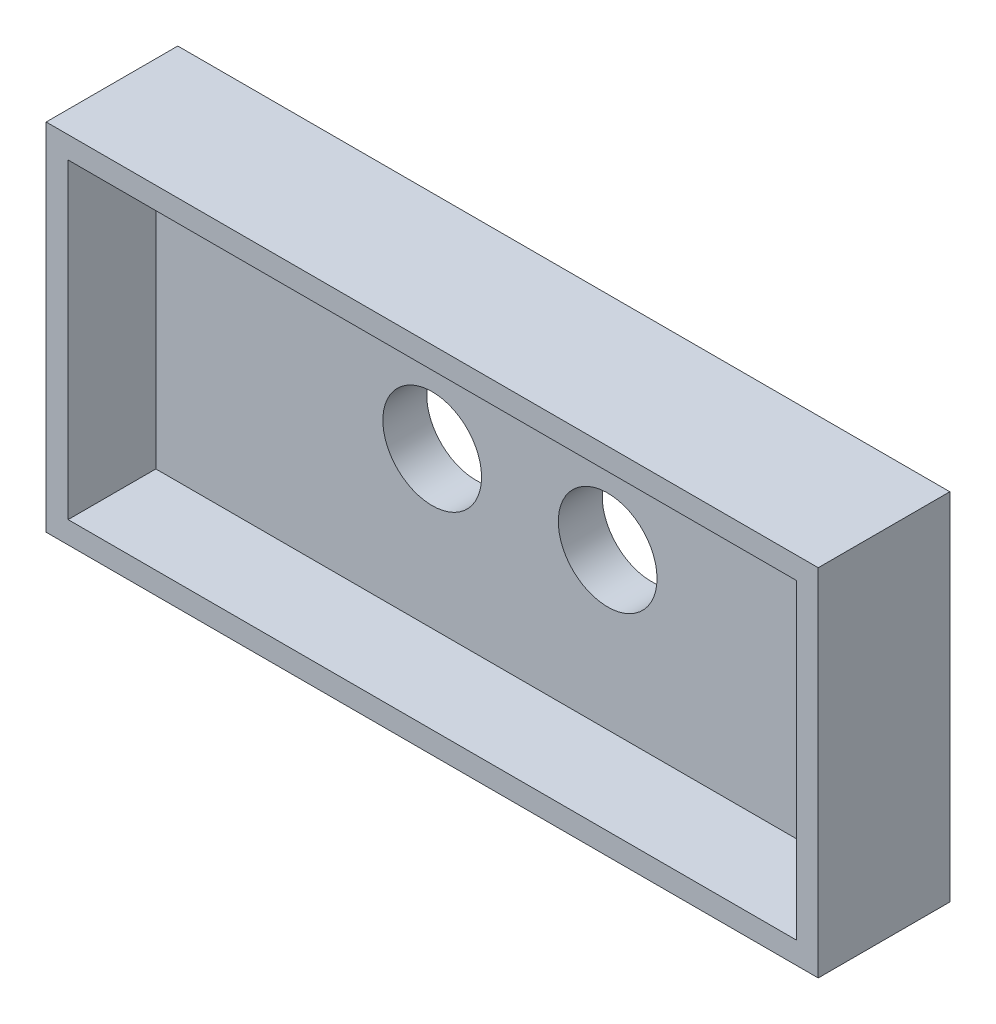
SolidWorks part; units mm, degrees
ref_plane "Front Plane" through (0, 0, 0) normal (0, 0, 1) x (1, 0, 0)
ref_plane "Top Plane" through (0, 0, 0) normal (0, 1, 0) x (1, 0, 0)
ref_plane "Right Plane" through (0, 0, 0) normal (1, 0, 0) x (0, 0, -1)
sketch "Sketch1" plane through (0, 0, 0) normal (0, 0, 1) x (1, 0, 0)
  line L0 (-105.41, 0) -> (105.41, 0) construction
  line L1 (0, 45.085) -> (0, -45.085) construction
  line L2 (105.41, -51.435) -> (111.76, -51.435)
  line L3 (-105.41, -45.085) -> (105.41, -45.085)
  line L4 (-105.41, -45.085) -> (-105.41, 45.085)
  line L5 (-105.41, 45.085) -> (105.41, 45.085)
  line L6 (105.41, -45.085) -> (105.41, 45.085)
  line L7 (-105.41, -45.085) -> (105.41, 45.085) construction
  line L8 (-105.41, 45.085) -> (105.41, -45.085) construction
  line L9 (-105.41, 45.085) -> (105.41, 45.085)
  line L10 (-105.41, 45.085) -> (-105.41, 51.435)
  line L11 (-105.41, 51.435) -> (105.41, 51.435)
  line L12 (105.41, 45.085) -> (105.41, 51.435)
  line L13 (-105.41, -45.085) -> (105.41, -45.085)
  line L14 (-105.41, -45.085) -> (-105.41, -51.435)
  line L15 (-105.41, -51.435) -> (105.41, -51.435)
  line L16 (105.41, -45.085) -> (105.41, -51.435)
  line L17 (-105.41, 51.435) -> (-111.76, 51.435)
  line L18 (-105.41, 51.435) -> (-105.41, -51.435)
  line L19 (-105.41, -51.435) -> (-111.76, -51.435)
  line L20 (-111.76, 51.435) -> (-111.76, -51.435)
  line L21 (111.76, 51.435) -> (111.76, -51.435)
  line L22 (105.41, 51.435) -> (111.76, 51.435)
  circle A0 centre (-25.4, 0) radius 14.2875
  circle A1 centre (25.4, 0) radius 14.2875
  point P8 (0, 0)
  dimension "D1" = 28.575
  dimension "D2" = 50.8
  dimension "D3" = 90.17
  dimension "D4" = 210.82
  dimension "D5" = 6.35
  dimension "D6" = 6.35
  dimension "D7" = 6.35
extrude "Boss-Extrude1" add sketch "Sketch1" along normal blind 25.4 and the other way blind 12.7 contours L5 L12 L11 L10 | L17 L20 L19 L14 L4 L10 | L16 L3 L14 L15 | L22 L12 L6 L16 L2 L21 region at (108.585, 0, 0) region at (0, -48.26, 0) region at (-108.585, 0, 0) region at (0, 48.26, 0)
extrude "Boss-Extrude2" add sketch "Sketch1<3>" against normal blind 12.7 contours L3 L6 L5 L4 A1 A0 region at (0, 0, 0)
sketch "Sketch1<3>" plane through (0, 0, 0) normal (0, 0, 1) x (1, 0, 0) same geometry as "Sketch1"
